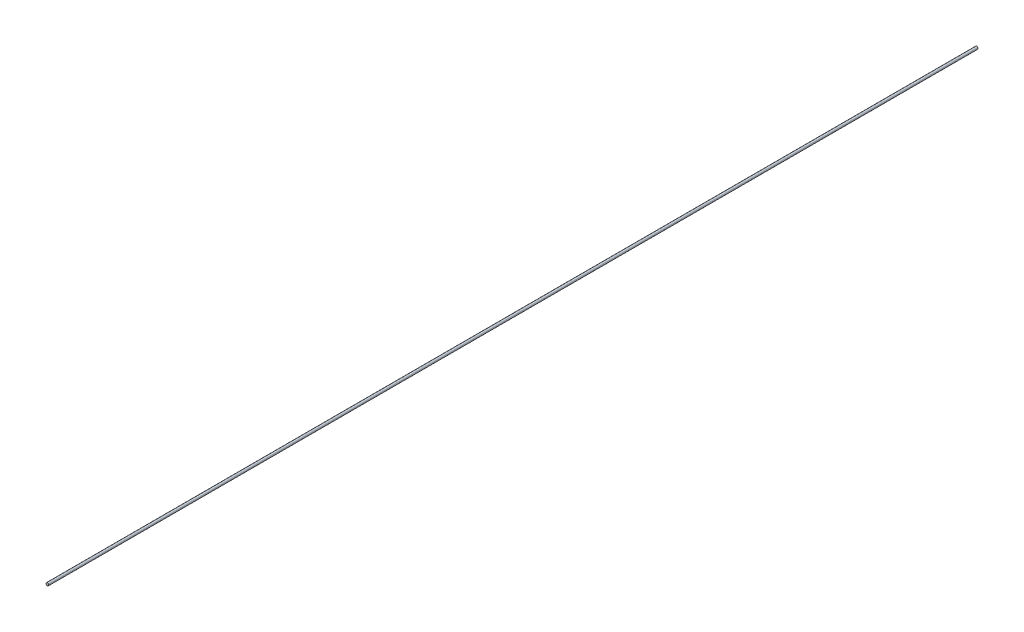
SolidWorks part; units mm, degrees
ref_plane "Front Plane" through (0, 0, 0) normal (0, 0, 1) x (1, 0, 0)
ref_plane "Top Plane" through (0, 0, 0) normal (0, 1, 0) x (1, 0, 0)
ref_plane "Right Plane" through (0, 0, 0) normal (1, 0, 0) x (0, 0, -1)
sketch "Sketch1" plane through (0, 0, 0) normal (0, 1, 0) x (1, 0, 0)
  line L0 (-3.0138, 802.4439) -> (-3.0138, -86.5561)
revolve "Revolve-Thin1" add sketch "Sketch1" angle 360 about L0 wall 1.27
ref_point "Point2"
ref_point "Point4"
